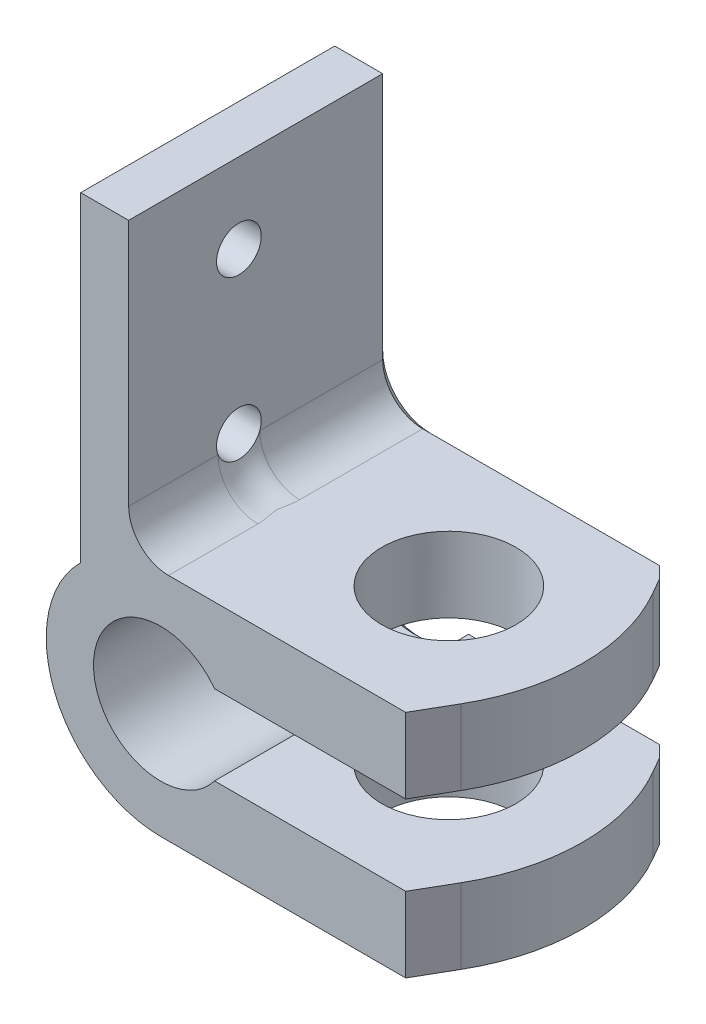
SolidWorks part; units mm, degrees
material "ABS"
ref_plane "Front Plane" through (0, 0, 0) normal (0, 0, 1) x (1, 0, 0)
ref_plane "Top Plane" through (0, 0, 0) normal (0, 1, 0) x (1, 0, 0)
ref_plane "Right Plane" through (0, 0, 0) normal (1, 0, 0) x (0, 0, -1)
ref_plane "Plane4" through (0, 0, 16.4) normal (0, 0, 1) x (1, 0, 0)
sketch "Sketch1" plane through (0, 0, 16.4) normal (0, 0, 1) x (1, 0, 0)
  line L0 (7.2, 0) -> (22.5, 0)
  line L1 (22.5, 0) -> (22.5, 14.4)
  line L2 (22.5, 14.4) -> (7.2, 14.4)
  arc A0 (7.2, 14.4) -> (7.2, 0) centre (7.2, 7.2) ccw
  dimension "D1" = 15.3
  dimension "D16" = 14.4
extrude "Boss-Extrude1" add sketch "Sketch1" against normal blind 16.4
sketch "Sketch2" plane through (0, 0, 0) normal (0, 0, -1) x (-1, 0, 0)
  line L0 (-22.5, 9.7) -> (-22.5, 4.7)
  line L1 (-22.5, 4.7) -> (-10.5327, 4.7)
  line L18 (-10.5327, 9.7) -> (-22.5, 9.7)
  arc A0 (-10.5327, 9.7) -> (-10.5327, 4.7) centre (-7.1578, 7.2) cw
  dimension "D1" = 4.2
extrude "Cut-Extrude1" cut sketch "Sketch2" against normal through all
sketch "Sketch4" plane through (0, 9.7, 0) normal (0, -1, 0) x (1, 0, 0)
  circle A1 centre (17, 8.2) radius 4.2
  dimension "D1" = 8.4
extrude "Cut-Extrude3" cut sketch "Sketch4" against normal through all both and the other way through all
sketch "Sketch5" plane through (0, 14.4, 0) normal (0, 1, 0) x (1, 0, 0)
  line L0 (22.5, 0) -> (22.5, -16.4)
  line L1 (22.5, -16.4) -> (27.2343, -8.2)
  line L2 (27.2343, -8.2) -> (22.5, 0)
  dimension "D1" = 30
extrude "Boss-Extrude2" add sketch "Sketch5" against normal up to surface (9.7 mm away)
ref_plane "Plane5" through (0, 7.2, 0) normal (0, -1, 0) x (-1, 0, 0)
mirror "Mirror3" about plane through (0, 7.2, 0) normal (0, -1, 0) of "Boss-Extrude2"
sketch "Sketch6" plane through (22.5, 0, 0) normal (-1, 0, 0) x (0, 0, 1)
  line L4 (0, 9.7) -> (0, 4.7)
  line L5 (0, 4.7) -> (16.4, 4.7)
  line L6 (16.4, 4.7) -> (16.4, 9.7)
  line L7 (16.4, 9.7) -> (0, 9.7)
  line L8 (0, 9.7) -> (0, 4.7)
  line L9 (0, 4.7) -> (16.4, 4.7)
  line L10 (16.4, 4.7) -> (16.4, 9.7)
  line L11 (16.4, 9.7) -> (0, 9.7)
  dimension "D1" = 0
extrude "Cut-Extrude4" cut sketch "Sketch6" against normal blind 10
fillet "Fillet1" radius 12 2 edges at (27.2343, 12.05, 8.2) (27.2343, 2.35, 8.2)
sketch "Sketch7" plane through (0, 0, 0) normal (0, 0, -1) x (-1, 0, 0)
  line L1 (-7.2, 14.4) -> (-5.1578, 14.4)
  line L2 (-2.1578, 12.3397) -> (-2.1578, 32.4)
  line L3 (-2.1578, 32.4) -> (-5.1578, 32.4)
  line L4 (-5.1578, 14.4) -> (-5.1578, 32.4)
  arc A0 (-10.5327, 4.7) -> (-10.5327, 9.7) centre (-7.1578, 7.2) ccw construction
  arc A1 (-7.2, 0) -> (-7.2, 14.4) centre (-7.2, 7.2) ccw construction
  arc A2 (-2.1578, 12.3397) -> (-7.2, 14.4) centre (-7.2, 7.2) ccw
  dimension "D3" = 5
  dimension "D1" = 3
  dimension "D2" = 18
extrude "Boss-Extrude3" add sketch "Sketch7" against normal up to surface (16.4 mm away) up to face at (13.8363, 7.2, 16.4)
sketch "Sketch8" plane through (5.1578, 0, 0) normal (1, 0, 0) x (0, 0, -1)
  line L0 (-9.5, 33.4) -> (-9.5, 16.2828) construction
  line L1 (-16.4, 32.4) -> (0, 32.4) construction
  line L4 (0, 32.4) -> (0, 14.4) construction
  circle A0 centre (-9.5, 27.4) radius 1.4
  circle A1 centre (-9.5, 17.4) radius 1.4
  dimension "D1" = 10
  dimension "D3" = 2.8
  dimension "D2" = 5
  dimension "D4" = 9.5
extrude "Cut-Extrude5" cut sketch "Sketch8" against normal blind 10
fillet "Fillet2" radius 2.5 1 edges at (5.1578, 14.4, 8.2)
chamfer "Chamfer1" distance 0.5 angle 45 12 edges at (22.5, 2.35, 0) (14.85, 0, 0) (0.535, 4.4765, 0) (2.1578, 22.3698, 0) (3.6578, 32.4, 0) (5.1578, 24.65, 0) (5.89, 15.1322, 0) (15.0789, 14.4, 0) (22.5, 12.05, 0) (16.5163, 4.7, 0) (16.5163, 9.7, 0) (2.9578, 7.2, 0)
